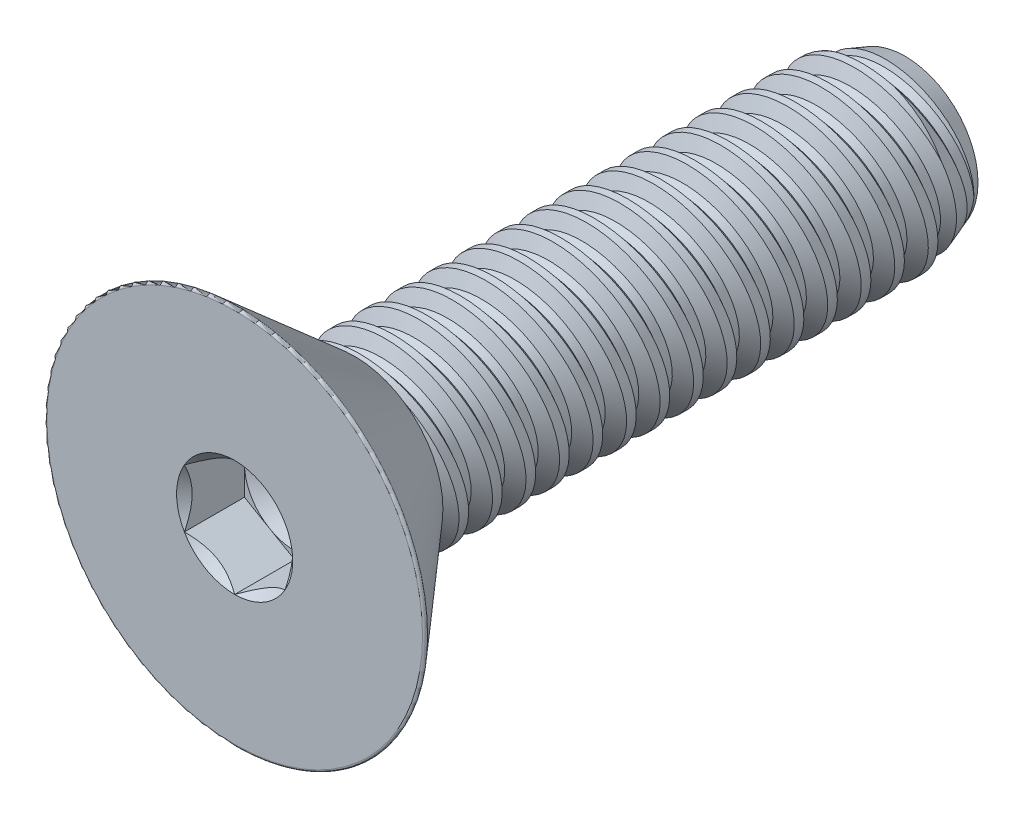
SolidWorks part; units mm, degrees
ref_plane "Front" through (0, 0, 0) normal (0, 0, 1) x (1, 0, 0)
ref_plane "Top" through (0, 0, 0) normal (0, 1, 0) x (1, 0, 0)
ref_plane "Right" through (0, 0, 0) normal (1, 0, 0) x (0, 0, -1)
sketch "Sketch1" plane through (0, 0, 0) normal (1, 0, 0) x (0, 0, -1)
  line L0 (0, 0) -> (-2.8448, 0) construction
  line L1 (0, 0) -> (13.0302, 0)
  line L2 (0, 0) -> (0, 2.0828)
  line L3 (0, 2.0828) -> (13.0302, 2.0828)
  line L4 (13.0302, 0) -> (13.0302, 2.0828)
  line L5 (0, -2.0828) -> (13.0302, -2.0828) construction
  dimension "D1" = 13.0302
  dimension "Thread Dia" = 4.1656
  dimension "Length" = 15.875
  dimension "Head Height" = 2.8448
revolve "Revolve1" add sketch "Sketch1" angle 360 about L0
ref_plane "Plane1" through (0, 0, 2.8448) normal (0, 0, 1) x (1, 0, 0)
sketch "Sketch2" plane through (0, 0, 0) normal (1, 0, 0) x (0, 0, -1)
  line L0 (0, 2.0828) -> (0, -2.0828) construction
  line L1 (0, -2.0828) -> (0.7938, -2.0828) construction
  line L2 (0.7938, -2.0828) -> (0, 2.0828) construction
  line L3 (0, 2.0828) -> (0.0975, 2.1014) construction
  line L4 (0.0975, 2.1014) -> (0.7797, 2.2314)
  line L5 (0.7797, 2.2314) -> (0.6165, 1.7629)
  line L6 (0.6165, 1.7629) -> (0.4215, 1.7258)
  line L7 (0.4215, 1.7258) -> (0.0975, 2.1014)
  line L8 (0.519, 1.7443) -> (0.4386, 2.1664) construction
  line L9 (0, -2.0828) -> (13.0302, -2.0828) construction
  line L10 (0, 2.0828) -> (13.0302, 2.0828) construction
  line L12 (0.4545, 2.0828) -> (1.2483, -2.0828) construction
  line L13 (0, -0.1622) -> (1.7028, 0.1622) construction
  line L15 (0, 0) -> (0, 2.0828) construction
  point P19 (0.8514, 0)
  dimension "D1" = 60
  dimension "Thread Pitch" = 0.7937
  dimension "D2" = 0.0992
  dimension "D3" = 0.1984
  dimension "D4" = 0.7937
revolve "Cut-Revolve1" cut sketch "Sketch2" angle 360 about L13
sketch "Sketch3" plane through (0, 0, 0) normal (1, 0, 0) x (0, 0, -1)
  line L0 (13.0302, 1.7258) -> (12.0493, 2.0828)
  line L1 (12.0493, 2.0828) -> (13.0302, 2.0828)
  line L2 (13.0302, 2.0828) -> (13.0302, 1.7258)
  line L3 (0, 2.0828) -> (13.0302, 2.0828) construction
  line L4 (13.0302, 0) -> (13.0302, 2.0828) construction
  line L5 (12.0493, 0) -> (0, 0) construction
  line L6 (12.0493, 2.0828) -> (12.0493, -2.0828) construction
  line L7 (0, -2.0828) -> (13.0302, -2.0828) construction
  dimension "D1" = 20
  dimension "D2" = 4.1656
revolve "Cut-Revolve2" cut sketch "Sketch3" angle 360 about L5
pattern_linear "LPattern1" count 16 spacing 0.7937 along (0, 0, 1)
pattern_linear "LPattern2" count 2 spacing 0.7937 along (0, 0, 1)
sketch "Sketch4" plane through (0, 0, 0) normal (0, 0, 1) x (1, 0, 0)
  circle A0 centre (0, 0) radius 4.5593
  dimension "Head Dia" = 9.1186
extrude "Extrude1" add sketch "Sketch4" along normal up to surface (2.8448 mm away)
sketch "Sketch9" plane through (0, 0, 0) normal (1, 0, 0) x (0, 0, -1)
  line L0 (-2.8448, 4.5593) -> (0, 2.0864)
  line L1 (0, 2.0864) -> (0, 4.5593)
  line L2 (0, 4.5593) -> (-2.8448, 4.5593)
  line L3 (0, 0) -> (-2.8448, 0) construction
  line L6 (-2.8448, -4.5593) -> (0, -2.0864) construction
  line L7 (0, -4.5593) -> (0, 4.5593) construction
  line L8 (-2.8448, 4.5593) -> (-2.8448, -4.5593) construction
  line L9 (0, 4.5593) -> (-2.8448, 4.5593) construction
  dimension "D1" = 82
revolve "Cut-Revolve3" cut sketch "Sketch9" angle 360 about L3
fillet "Fillet1" radius 0.0508
sketch "Sketch6" plane through (0, 0, 2.8448) normal (0, 0, 1) x (1, 0, 0)
  line L1 (0, -1.3748) -> (1.1906, -0.6874)
  line L2 (1.1906, -0.6874) -> (1.1906, 0.6874)
  line L3 (1.1906, 0.6874) -> (0, 1.3748)
  line L4 (0, 1.3748) -> (-1.1906, 0.6874)
  line L5 (-1.1906, 0.6874) -> (-1.1906, -0.6874)
  line L6 (-1.1906, -0.6874) -> (0, -1.3748)
  circle A0 centre (0, 0) radius 1.1906 construction
  dimension "Hex" = 2.3813
extrude "Cut-Extrude1" cut sketch "Sketch6" against normal blind 1.4224
sketch "Sketch7" plane through (0, 0, 2.8448) normal (0, 0, 1) x (1, 0, 0)
  circle A0 centre (0, 0) radius 1.3748
extrude "Cut-Extrude4" cut sketch "Sketch7" against normal blind 1.4224 draft 45
sketch "Sketch8" plane through (0, 0, 1.4224) normal (0, 0, 1) x (1, 0, 0)
  circle A0 centre (0, 0) radius 1.1906 construction
  circle A1 centre (0, 0) radius 1.1906
extrude "Cut-Extrude5" cut sketch "Sketch8" against normal blind 0.4741 draft 60
equation "\"D2@Sketch2\"=\"Thread Pitch@Sketch2\"/8"
equation "\"D3@Sketch2\"=\"Thread Pitch@Sketch2\"/4"
equation "\"D4@Sketch2\"=\"Thread Pitch@Sketch2\""
equation "\"D3@LPattern1\"=\"Thread Pitch@Sketch2\""
equation "\"D1@Cut-Extrude1\"=\"Head Height@Sketch1\"/2"
equation "\"D1@Cut-Extrude4\"=\"D1@Cut-Extrude1\""
equation "\"D1@Cut-Extrude5\"=\"D1@Cut-Extrude1\"/3"
equation "\"D1@LPattern1\"=\"D1@Sketch1\"/\"Thread Pitch@Sketch2\""
equation "\"D3@LPattern2\"=\"Thread Pitch@Sketch2\""
